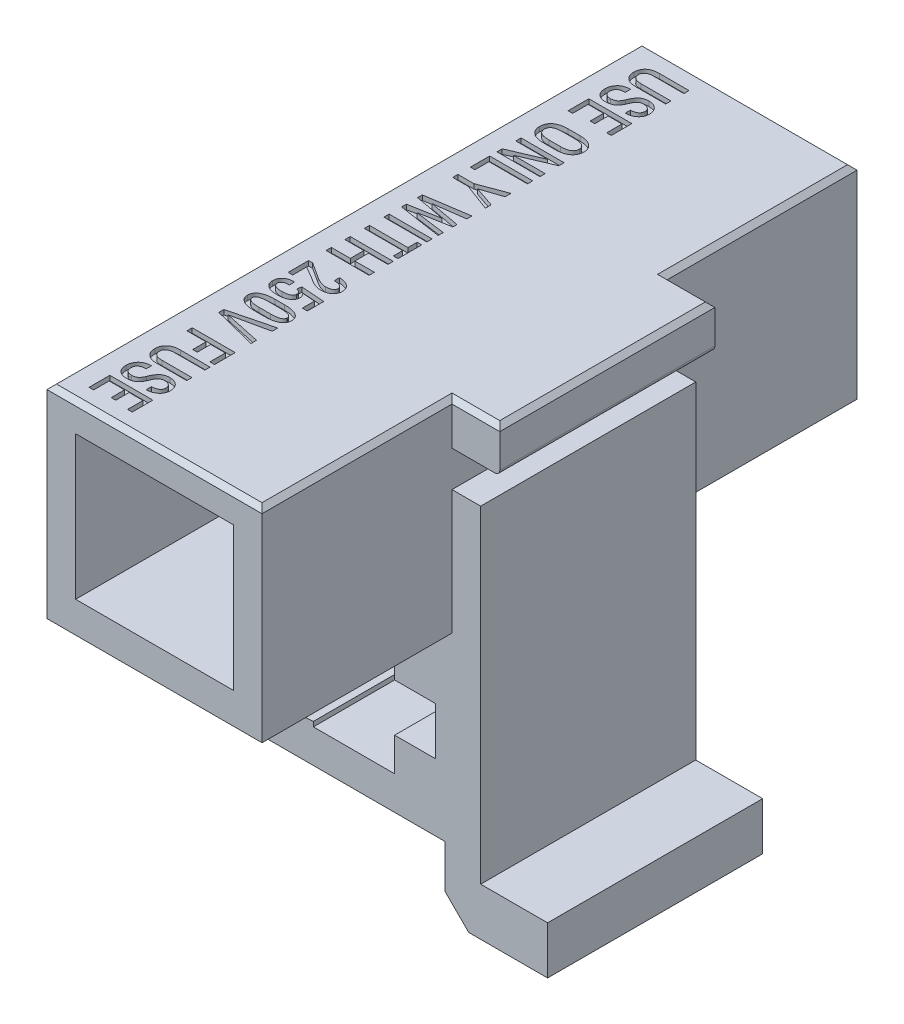
SolidWorks part; units mm, degrees
material "ABS"
ref_plane "Спереди" through (0, 0, 0) normal (0, 0, 1) x (1, 0, 0)
ref_plane "Сверху" through (0, 0, 0) normal (0, 1, 0) x (1, 0, 0)
ref_plane "Справа" through (0, 0, 0) normal (1, 0, 0) x (0, 0, -1)
sketch "Эскиз1" plane through (0, 0, 0) normal (0, 0, 1) x (1, 0, 0)
  line L1 (0, -10) -> (3.2, -10.2)
  line L2 (3.2, -10.2) -> (3.2, -10)
  line L3 (3.2, -10) -> (6.6, -10)
  line L4 (6.6, -10) -> (6.6, -11.4)
  line L5 (6.6, -11.4) -> (8.3, -11.4)
  line L6 (8.3, -11.4) -> (8.3, -13.4)
  line L7 (8.3, -13.4) -> (6.6, -13.4)
  line L8 (6.6, -13.4) -> (6.6, -14.8)
  line L9 (6.6, -14.8) -> (3.2, -14.8)
  line L10 (3.2, -14.8) -> (3.2, -14.6)
  line L11 (3.2, -14.6) -> (0, -14.8)
  line L12 (0, -14.8) -> (0, -16.2)
  line L13 (0, -16.2) -> (8.7, -16.2)
  line L14 (8.7, -16.2) -> (8.7, -18)
  line L15 (8.7, -18) -> (9.7, -19)
  line L16 (9.7, -19) -> (13, -19)
  line L17 (13, -19) -> (13, -17)
  line L18 (13, -17) -> (10.2, -17)
  line L19 (10.2, -17) -> (10.2, -3.3)
  line L20 (10.2, -3.3) -> (9, -3.3)
  line L21 (9, -3.3) -> (9, -1.8)
  line L22 (9, -1.8) -> (11, -1.8)
  line L23 (11, -1.8) -> (11, 0)
  line L24 (11, 0) -> (0, 0)
  line L26 (0, -10) -> (0, 0)
  line L27 (4.5, -12.4) -> (8.3, -12.4) construction
  line L28 (1.2, -7.2) -> (7.8, -7.2)
  line L29 (1.2, -7.2) -> (1.2, -1.2)
  line L30 (1.2, -1.2) -> (7.8, -1.2)
  line L31 (7.8, -7.2) -> (7.8, -1.2)
  line L32 (4.5, -1.2) -> (4.5, -7.2) construction
  line L33 (1.2, -4.2) -> (7.8, -4.2) construction
  circle A0 centre (4.5, -12.4) radius 2.3 construction
  point P0 (4.5, -4.2)
  dimension "D24" = 4.6
  dimension "D1" = 2.8
  dimension "D2" = 2
  dimension "D3" = 4.8
  dimension "D4" = 0.2
  dimension "D5" = 16.2
  dimension "D6" = 10.2
  dimension "D7" = 8.3
  dimension "D8" = 6.6
  dimension "D9" = 3.2
  dimension "D10" = 19
  dimension "D11" = 2
  dimension "D12" = 4.3
  dimension "D13" = 8.7
  dimension "D14" = 135
  dimension "D15" = 1
  dimension "D16" = 1.8
  dimension "D17" = 11
  dimension "D18" = 1.2
  dimension "D19" = 1.5
  dimension "D20" = 6.6
  dimension "D21" = 6
  dimension "D22" = 1.2
  dimension "D23" = 1.2
  dimension "D25" = 3.8
extrude "Тело_держателя" add sketch "Эскиз1" along normal mid plane 9
sketch "Эскиз2" plane through (0, 0, 0) normal (0, 0, 1) x (1, 0, 0)
  line L0 (9, -3.3) -> (9, -1.8) construction
  line L1 (0, 0) -> (9, 0)
  line L2 (0, 0) -> (0, -8.5)
  line L3 (0, -8.5) -> (9, -8.5)
  line L4 (9, 0) -> (9, -8.5)
  line L6 (1.2, -1.2) -> (7.8, -1.2)
  line L7 (1.2, -1.2) -> (1.2, -7.2)
  line L8 (1.2, -7.2) -> (7.8, -7.2)
  line L9 (7.8, -1.2) -> (7.8, -7.2)
  dimension "D1" = 8.5
extrude "Расширение" add sketch "Эскиз2" along normal mid plane 24.9
sketch "Эскиз3" plane through (0, 0, 0) normal (0, 0, 1) x (1, 0, 0)
  line L0 (2.5, -1.2) -> (2.5, -2.2345)
  line L1 (1.2, -1.2) -> (7.8, -1.2) construction
  line L2 (4.5, -1.2) -> (4.5, -7.2) construction
  line L3 (4.5, -2.2) -> (4.5, -1.2) construction
  line L4 (6.5, -1.2) -> (2.5, -1.2)
  line L5 (6.5, -1.2) -> (6.5, -2.2345)
  arc A0 (2.9598, -2.4883) -> (2.5, -2.2345) centre (2.8, -2.2345) cw
  arc A1 (6.0402, -2.4883) -> (6.5, -2.2345) centre (6.2, -2.2345) ccw
  ellipse E0 centre (4.5, -2.7) end of major axis (6.2, -2.7) minor radius 0.5 (6.0402, -2.4883) -> (2.9598, -2.4883) ccw
  dimension "D1" = 0.3
  dimension "D2" = 2
  dimension "D3" = 0.5
  dimension "D4" = 3.4
  dimension "D5" = 5
extrude "Поддержка_предохранителя" add sketch "Эскиз3" along normal mid plane 5
ref_axis "Ось_предохранителя" through (4.5, -12.4, -13.2922) along (0, 0, 1)
fillet "Скругление1" radius 0.2 1 edges at (11, -1.8, 0)
sketch "Эскиз5" plane through (0, 0, 0) normal (0, 1, 0) x (1, 0, 0)
  line L0 (1, 12.45) -> (1, -12.45) construction
  line L1 (9, -12.45) -> (0, -12.45) construction
  line L2 (9, 12.45) -> (0, 12.45) construction
  text T0 "USE ONLY WITH 250V FUSE" font "Roboto Condensed" height 1.8
  dimension "D1" = 1
extrude "Вырез-Вытянуть2" cut sketch "Эскиз5" against normal blind 0.2
chamfer "Фаска1" distance 0.2 angle 45 8 edges at (4.5, 0, 12.45) (0, 0, 0) (4.5, 0, -12.45) (9, 0, -8.475) (10, 0, -4.5) (9, 0, 8.475) (10, 0, 4.5) (11, 0, 0)
